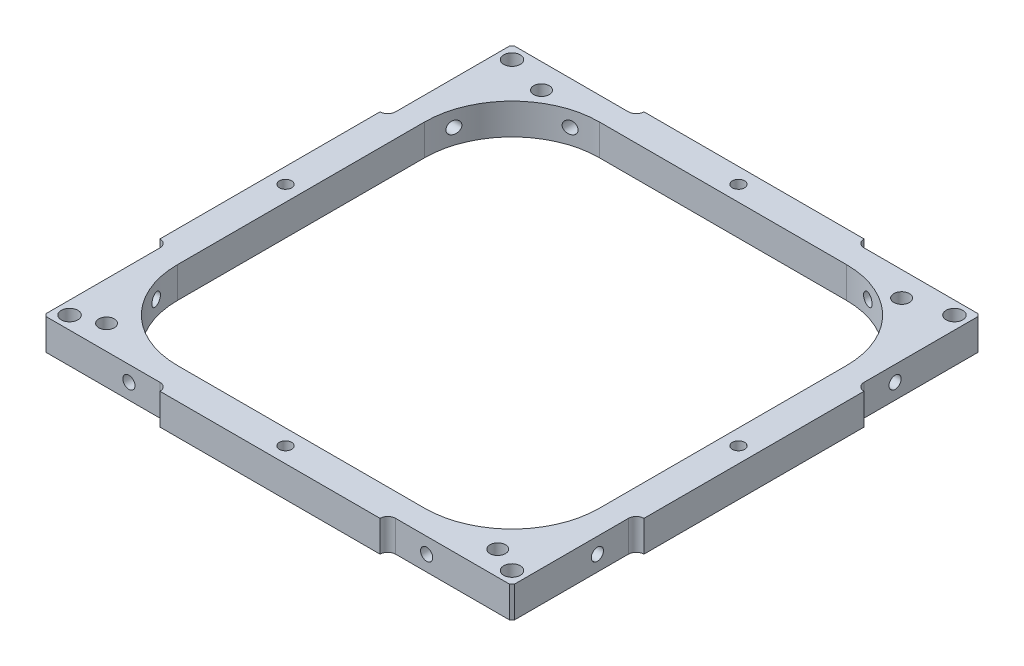
SolidWorks part; units mm, degrees
material "6061-T6 (SS)"
ref_plane "Front Plane" through (0, 0, 0) normal (0, 0, 1) x (1, 0, 0)
ref_plane "Top Plane" through (0, 0, 0) normal (0, 1, 0) x (1, 0, 0)
ref_plane "Right Plane" through (0, 0, 0) normal (1, 0, 0) x (0, 0, -1)
sketch "Sketch1" plane through (0, 0, 0) normal (0, 1, 0) x (1, 0, 0)
  line L0 (-49.5, 22.5125) -> (-47.9125, 22.5125)
  line L1 (-49.5, -49.5) -> (49.5, -49.5)
  line L2 (-49.5, -49.5) -> (-49.5, 49.5)
  line L3 (-49.5, 49.5) -> (49.5, 49.5)
  line L4 (49.5, -49.5) -> (49.5, 49.5)
  line L5 (-49.5, -49.5) -> (49.5, 49.5) construction
  line L6 (-49.5, 49.5) -> (49.5, -49.5) construction
  line L7 (-47.9125, 22.5125) -> (-47.9125, 47.9125)
  line L8 (-47.9125, 47.9125) -> (-22.5125, 47.9125)
  line L9 (-22.5125, 47.9125) -> (-22.5125, 49.5)
  line L10 (22.5125, 49.5) -> (22.5125, 47.9125)
  line L11 (22.5125, 47.9125) -> (47.9125, 47.9125)
  line L12 (47.9125, 47.9125) -> (47.9125, 22.5125)
  line L13 (47.9125, 22.5125) -> (49.5, 22.5125)
  line L14 (49.5, -22.5125) -> (47.9125, -22.5125)
  line L15 (47.9125, -22.5125) -> (47.9125, -47.9125)
  line L16 (47.9125, -47.9125) -> (22.5125, -47.9125)
  line L17 (22.5125, -47.9125) -> (22.5125, -49.5)
  line L18 (-22.5125, -49.5) -> (-22.5125, -47.9125)
  line L19 (-22.5125, -47.9125) -> (-47.9125, -47.9125)
  line L20 (-47.9125, -47.9125) -> (-47.9125, -22.5125)
  line L21 (-47.9125, -22.5125) -> (-49.5, -22.5125)
  point P0 (0, 0)
  dimension "D1" = 99
  dimension "D2" = 99
  dimension "D3" = 26.9875
  dimension "D4" = 1.5875
  dimension "D5" = 26.9875
  dimension "D6" = 1.5875
extrude "Boss-Extrude1" add sketch "Sketch1" along normal blind 6.35 contours L21 L20 L19 L18 L1 L17 L16 L15 L14 L4 L13 L12 L11 L10 L3 L9 L8 L7 L0 L2 region at (0, 0, 0)
chamfer "Chamfer1" distance 0.508 angle 45 4 edges at (47.9125, 3.175, -47.9125) (-47.9125, 3.175, -47.9125) (-47.9125, 3.175, 47.9125) (47.9125, 3.175, 47.9125)
fillet "Fillet1" radius 1.5875 8 edges at (-47.9125, 3.175, -22.5125) (-22.5125, 3.175, -47.9125) (22.5125, 3.175, -47.9125) (47.9125, 3.175, -22.5125) (47.9125, 3.175, 22.5125) (22.5125, 3.175, 47.9125) (-22.5125, 3.175, 47.9125) (-47.9125, 3.175, 22.5125)
hole_wizard "M3 Clearance Hole1" positions "Sketch2" profile "Sketch3" hole size "M3" standard "ANSI Metric" end condition through all
sketch "Sketch2" plane through (0, 0, 0) normal (0, -1, 0) x (-1, 0, 0)
  line L0 (-49.5, -22.5125) -> (-49.5, 22.5125) construction
  line L1 (22.5125, 49.5) -> (-22.5125, 49.5) construction
  line L5 (49.5, -22.5125) -> (49.5, 22.5125) construction
  line L6 (22.5125, -49.5) -> (-22.5125, -49.5) construction
  point P0 (-45.25, 45.25)
  point P2 (45.25, 45.25)
  point P4 (45.25, -45.25)
  point P6 (-45.25, -45.25)
  dimension "D1" = 4.25
  dimension "D2" = 4.25
  dimension "D3" = 4.25
  dimension "D4" = 4.25
  dimension "D5" = 4.25
  dimension "D6" = 4.25
  dimension "D7" = 4.25
  dimension "D8" = 4.25
sketch "Sketch3" plane through (45.25, 0, -45.25) normal (1, 0, 0) x (0, 0, -1)
  line L0 (0, 0) -> (0, 6.35)
  line L1 (0, 6.35) -> (1.7, 6.35)
  line L2 (1.7, 6.35) -> (1.7, 0)
  line L5 (1.7, 0) -> (0, 0)
  line L11 (0, -6.35) -> (0, 107.95) construction
  dimension "Thru Hole Dia." = 3.4
  dimension "Thru Hole Depth" = 6.35
hole_wizard "M3x0.5 Tapped Hole1" positions "Sketch6" profile "Sketch7" tap size "M3x0.5" standard "ANSI Metric"
sketch "Sketch6" plane through (0, 0, 47.9125) normal (0, 0, 1) x (1, 0, 0)
  line L1 (-24.1, 0) -> (-47.4045, 0) construction
  line L4 (47.4045, 0) -> (24.1, 0) construction
  line L5 (-24.1, 0) -> (-24.1, 6.35) construction
  line L7 (24.1, 6.35) -> (24.1, 0) construction
  point P0 (-30.45, 3.175)
  point P2 (30.45, 3.175)
  dimension "D1" = 6.35
  dimension "D2" = 3.175
  dimension "D3" = 6.35
  dimension "D4" = 3.175
sketch "Sketch7" plane through (-30.45, 3.175, 47.9125) normal (1, 0, 0) x (0, -1, 0)
  line L0 (0, 0) -> (0, 8.3711)
  line L1 (0, 8.3711) -> (1.25, 7.62)
  line L2 (1.25, 7.62) -> (1.25, 0)
  line L5 (1.25, 0) -> (0, 0)
  line L10 (0, 8.3711) -> (-1.25, 7.62) construction
  line L11 (0, -6.35) -> (0, 107.95) construction
  dimension "Tap Drill Dia." = 2.5
  dimension "Tap Drill Depth" = 7.62
  dimension "Drill Angle" = 118
cosmetic thread "Hole Thread1" parameters "D1"=4.7625, "D2"=3
cosmetic thread "Hole Thread2" parameters "D1"=4.7625, "D2"=3
ref_plane "Plane1" through (0, 0, 0) normal (0, 0, 1) x (1, 0, 0)
ref_plane "Plane2" through (0, 0, 0) normal (-1, 0, 0) x (0, 0, 1)
ref_axis "Axis1" through (0, -0.3175, 0) along (0, 1, 0)
pattern_circular "CirPattern1" count 4 over 360 about axis through (0, -0.3175, 0) along (0, 1, 0) of "M3x0.5 Tapped Hole1"
sketch "Sketch9" plane through (0, 6.35, 0) normal (0, 1, 0) x (1, 0, 0)
  line L0 (0, 3.4925) -> (0, -3.4925) construction
  line L1 (-3.4925, 0) -> (3.4925, 0) construction
  circle A0 centre (-40.005, -42.926) radius 1.5875
  circle A1 centre (40.005, -42.926) radius 1.5875
  circle A2 centre (36.83, 42.8625) radius 1.5875
  circle A3 centre (-36.83, 42.8625) radius 1.5875
  dimension "D7" = 3.175
  dimension "D1" = 40.005
  dimension "D2" = 40.005
  dimension "D3" = 36.83
  dimension "D4" = 36.83
  dimension "D5" = 42.8625
  dimension "D6" = 42.926
extrude "Cut-Extrude2" cut sketch "Sketch9" against normal through all
sketch "Sketch11" plane through (0, 6.35, 0) normal (0, 1, 0) x (1, 0, 0)
  line L0 (-22.5125, 49.5) -> (22.5125, 49.5) construction
  line L1 (-43.15, -43.15) -> (43.15, -43.15)
  line L2 (-43.15, -43.15) -> (-43.15, 43.15)
  line L3 (-43.15, 43.15) -> (43.15, 43.15)
  line L4 (43.15, -43.15) -> (43.15, 43.15)
  line L5 (-43.15, -43.15) -> (43.15, 43.15) construction
  line L6 (-43.15, 43.15) -> (43.15, -43.15) construction
  line L7 (49.5, -22.5125) -> (49.5, 22.5125) construction
  line L8 (-44.2725, 42.0275) -> (42.0275, -44.2725)
  line L9 (-42.0275, -44.2725) -> (44.2725, 42.0275)
  line L10 (-42.0275, 44.2725) -> (44.2725, -42.0275)
  line L11 (-44.2725, -42.0275) -> (42.0275, 44.2725)
  circle A5 centre (-36.83, 42.8625) radius 4.7625
  circle A6 centre (-36.83, 42.8625) radius 4.7625
  circle A9 centre (36.83, 42.8625) radius 4.7625
  circle A10 centre (36.83, 42.8625) radius 4.7625
  circle A12 centre (-40.005, -42.926) radius 4.7625
  circle A13 centre (-40.005, -42.926) radius 4.7625
  circle A14 centre (0, 0) radius 25.4
  circle A15 centre (40.005, -42.926) radius 4.7625
  circle A16 centre (40.005, -42.926) radius 4.7625
  circle A17 centre (0, 0) radius 22.225
  point P0 (0, 0)
  dimension "D9" = 50.8
  dimension "D1" = 6.35
  dimension "D2" = 6.35
  dimension "D3" = 3.175
  dimension "D4" = 3.175
  dimension "D5" = 3.175
  dimension "D6" = 3.175
  dimension "D7" = 1.5875
  dimension "D8" = 1.5875
  dimension "D10" = 3.175
hole_wizard "M3x0.5 Tapped Hole3" positions "Sketch14" profile "Sketch15" tap size "M3x0.5" standard "ANSI Metric"
sketch "Sketch14" plane through (0, 6.35, 0) normal (0, 1, 0) x (1, 0, 0)
  line L0 (0, 3.4925) -> (0, -3.4925) construction
  line L1 (-22.5125, -49.5) -> (22.5125, -49.5) construction
  point P0 (0, -46.325)
  dimension "D1" = 3.175
sketch "Sketch15" plane through (0, 6.35, 46.325) normal (1, 0, 0) x (0, 0, 1)
  line L0 (0, 0) -> (0, 8.3711)
  line L1 (0, 8.3711) -> (1.25, 7.62)
  line L2 (1.25, 7.62) -> (1.25, 0)
  line L5 (1.25, 0) -> (0, 0)
  line L10 (0, 8.3711) -> (-1.25, 7.62) construction
  line L11 (0, -6.35) -> (0, 107.95) construction
  dimension "Tap Drill Dia." = 2.5
  dimension "Tap Drill Depth" = 7.62
  dimension "Drill Angle" = 118
cosmetic thread "Hole Thread5" parameters "D1"=6.096, "D2"=3
sketch "Sketch16" plane through (0, 6.35, 0) normal (0, 1, 0) x (1, 0, 0)
  line L0 (-22.5125, 49.5) -> (22.5125, 49.5) construction
  line L1 (-43.15, -43.15) -> (43.15, -43.15)
  line L2 (-43.15, -43.15) -> (-43.15, 43.15)
  line L3 (-43.15, 43.15) -> (43.15, 43.15)
  line L4 (43.15, -43.15) -> (43.15, 43.15)
  line L5 (-43.15, -43.15) -> (43.15, 43.15) construction
  line L6 (-43.15, 43.15) -> (43.15, -43.15) construction
  line L7 (49.5, -22.5125) -> (49.5, 22.5125) construction
  arc A0 (25.2587, 43.15) -> (43.15, 25.2587) centre (25.2587, 25.2587) cw
  arc A1 (43.15, -25.2587) -> (25.2587, -43.15) centre (25.2587, -25.2587) cw
  arc A2 (-25.2587, -43.15) -> (-43.15, -25.2587) centre (-25.2587, -25.2587) cw
  arc A3 (-43.15, 25.2587) -> (-25.2587, 43.15) centre (-25.2587, 25.2587) cw
  circle A4 centre (36.83, 42.8625) radius 3.175 construction
  circle A5 centre (36.83, 42.8625) radius 1.5875 construction
  point P0 (0, 0)
  dimension "D3" = 1.5875
  dimension "D1" = 6.35
  dimension "D2" = 6.35
extrude "Cut-Extrude3" cut sketch "Sketch16" against normal through all contours A3 L2 A2 L1 A1 L4 A0 L3 region at (0, 6.35, 0)
pattern_circular "CirPattern2" count 4 over 360 about axis through (0, -0.3175, 0) along (0, 1, 0) of "M3x0.5 Tapped Hole3"
